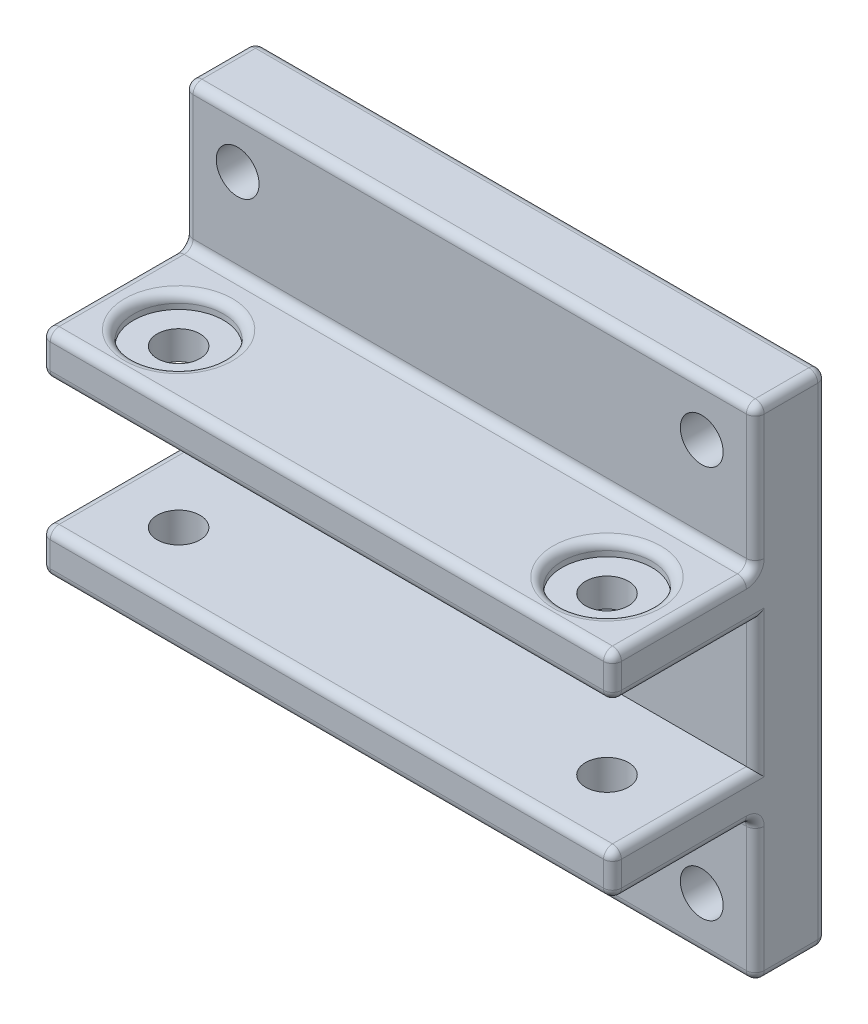
SolidWorks part; units mm, degrees
ref_plane "Front Plane" through (0, 0, 0) normal (0, 0, 1) x (1, 0, 0)
ref_plane "Top Plane" through (0, 0, 0) normal (0, 1, 0) x (1, 0, 0)
ref_plane "Right Plane" through (0, 0, 0) normal (1, 0, 0) x (0, 0, -1)
sketch "Sketch1" plane through (0, 0, 0) normal (0, 0, 1) x (1, 0, 0)
  line L1 (0, 0) -> (50.8, 0)
  line L2 (0, 0) -> (0, 44.45)
  line L3 (0, 44.45) -> (50.8, 44.45)
  line L4 (50.8, 0) -> (50.8, 44.45)
  dimension "D1" = 50.8
  dimension "D2" = 44.45
extrude "Boss-Extrude1" add sketch "Sketch1" along normal blind 6.35
ref_plane "Plane1" through (25.4, 0, 0) normal (1, 0, 0) x (0, 0, -1)
ref_plane "Plane2" through (0, 22.225, 0) normal (0, -1, 0) x (-1, 0, 0)
sketch "Sketch2" plane through (0, 0, 6.35) normal (0, 0, 1) x (1, 0, 0)
  line L0 (0, 44.45) -> (0, 0) construction
  line L1 (50.8, 44.45) -> (0, 44.45) construction
  circle A0 centre (4.7625, 39.6875) radius 1.905
  dimension "D2" = 4.7625
  dimension "D3" = 3.81
  dimension "D1" = 4.7625
extrude "Cut-Extrude1" cut sketch "Sketch2" against normal blind 6.35 contours A0
sketch "Sketch3" plane through (0, 0, 6.35) normal (0, 0, 1) x (1, 0, 0)
  line L0 (0, 44.45) -> (0, 0) construction
  line L1 (0, 31.75) -> (50.8, 31.75)
  line L2 (0, 31.75) -> (0, 27.94)
  line L3 (0, 27.94) -> (50.8, 27.94)
  line L4 (50.8, 31.75) -> (50.8, 27.94)
  line L6 (50.8, 0) -> (50.8, 44.45) construction
  line L8 (0, 12.7) -> (50.8, 12.7)
  line L9 (0, 12.7) -> (0, 16.51)
  line L10 (0, 16.51) -> (50.8, 16.51)
  line L11 (50.8, 12.7) -> (50.8, 16.51)
  line L12 (0, 0) -> (50.8, 0) construction
  dimension "D1" = 12.7
  dimension "D2" = 3.81
  dimension "D3" = 31.75
  dimension "D4" = 3.81
extrude "Boss-Extrude2" add sketch "Sketch3" along normal blind 12.7
sketch "Sketch4" plane through (0, 31.75, 0) normal (0, 1, 0) x (1, 0, 0)
  line L2 (50.8, 0) -> (0, 0) construction
  line L3 (0, -6.35) -> (0, 0) construction
  circle A1 centre (6.35, -13.1889) radius 1.905
  dimension "D1" = 13.1889
  dimension "D3" = 3.81
  dimension "D2" = 6.35
extrude "Cut-Extrude2" cut sketch "Sketch4" against normal through all both and the other way through all
ref_plane "Plane3" through (25.4, 0, 0) normal (1, 0, 0) x (0, 0, -1)
mirror "Mirror3" about plane through (25.4, 0, 0) normal (1, 0, 0) of "Cut-Extrude2"
sketch "Sketch5" plane through (0, 31.75, 0) normal (0, 1, 0) x (1, 0, 0)
  circle A0 centre (6.35, -13.1889) radius 4.0005
  circle A1 centre (44.45, -13.1889) radius 4.0005
  dimension "D1" = 8.001
extrude "Cut-Extrude3" cut sketch "Sketch5" against normal blind 1.27
fillet "Fillet1" radius 0.7937 36 edges at (25.4, 0, 6.35) (25.4, 0, 0) (0, 38.1, 6.35) (0, 31.75, 12.7) (0, 27.94, 12.7) (0, 22.225, 6.35) (0, 16.51, 12.7) (0, 12.7, 12.7) (0, 6.35, 6.35) (0, 0, 3.175) (0, 22.225, 0) (25.4, 31.75, 19.05) (25.4, 27.94, 19.05) (0, 29.845, 19.05) (25.4, 16.51, 19.05) (25.4, 12.7, 19.05) (0, 14.605, 19.05) (50.8, 0, 3.175) (50.8, 6.35, 6.35) (50.8, 12.7, 12.7) (50.8, 14.605, 19.05) (50.8, 16.51, 12.7) (50.8, 22.225, 6.35) (50.8, 27.94, 12.7) (50.8, 29.845, 19.05) (50.8, 31.75, 12.7) (50.8, 38.1, 6.35) (50.8, 22.225, 0) (50.8, 44.45, 3.175) (25.4, 44.45, 6.35) (0, 44.45, 3.175) (25.4, 44.45, 0) (6.35, 31.75, 17.1894) (44.45, 31.75, 17.1894) (25.4, 12.7, 6.35) (25.4, 31.75, 6.35)
sketch "Sketch6" plane through (0, 0, 0) normal (0, 0, -1) x (-1, 0, 0)
  line L0 (-50.8, 0.7937) -> (-50.8, 43.6562) construction
  line L5 (-44.45, 15.875) -> (-44.45, 0) construction
  line L6 (-0.7937, 0) -> (-50.0062, 0) construction
  circle A1 centre (-44.45, 15.875) radius 1.905
  dimension "D1" = 3.81
  dimension "D2" = 6.35
  dimension "D3" = 15.875
extrude "Cut-Extrude4" cut sketch "Sketch6" against normal blind 5.08
mirror "Mirror1" about plane through (25.4, 0, 0) normal (1, 0, 0) of "Cut-Extrude4", "Cut-Extrude1"
mirror "Mirror2" about plane through (0, 22.225, 0) normal (0, -1, 0) of "Mirror1", "Cut-Extrude1"
